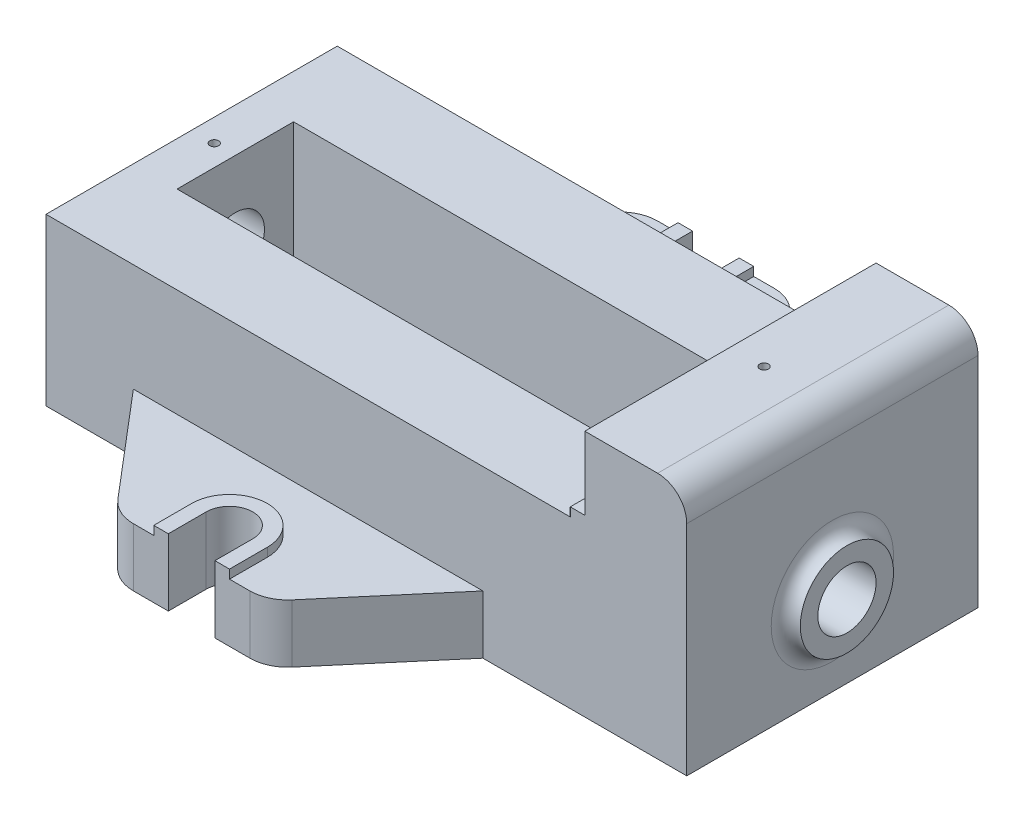
SolidWorks part; units mm, degrees
material "Gray Cast Iron"
ref_plane "Front Plane" through (0, 0, 0) normal (0, 0, 1) x (1, 0, 0)
ref_plane "Top Plane" through (0, 0, 0) normal (0, 1, 0) x (1, 0, 0)
ref_plane "Right Plane" through (0, 0, 0) normal (1, 0, 0) x (0, 0, -1)
sketch "Sketch1" plane through (0, 0, 0) normal (0, 1, 0) x (1, 0, 0)
  line L1 (-90, 50) -> (90, 50)
  line L2 (-90, 50) -> (-90, -50)
  line L3 (-90, -50) -> (90, -50)
  line L4 (90, 50) -> (90, -50)
  line L5 (-90, 50) -> (90, -50) construction
  line L6 (-90, -50) -> (90, 50) construction
  point P0 (0, 0)
  dimension "D1" = 180
  dimension "D2" = 100
extrude "Boss-Extrude1" add sketch "Sketch1" along normal blind 57
sketch "Sketch2" plane through (0, 0, 0) normal (0, 1, 0) x (1, 0, 0)
  line L0 (-90, -50) -> (90, -50) construction
  line L1 (-60, -50) -> (60, -50)
  line L2 (0, -69) -> (0, 49000) construction
  line L3 (-20, -90) -> (-8, -90)
  line L4 (-8, -90) -> (8, -90)
  line L8 (8, -90) -> (20, -90)
  line L9 (-60, -50) -> (-29.9068, -85.4175)
  line L10 (60, -50) -> (29.9068, -85.4175)
  arc A2 (-20, -90) -> (-29.9068, -85.4175) centre (-20, -77) cw
  arc A3 (20, -90) -> (29.9068, -85.4175) centre (20, -77) ccw
  point P18 (-25.4577, -88.7989)
  dimension "D4" = 40
  dimension "D5" = 40
  dimension "D6" = 120
  dimension "D7" = 13
extrude "Boss-Extrude2" add sketch "Sketch2" along normal blind 20
sketch "Sketch3" plane through (0, 20, 0) normal (0, 1, 0) x (1, 0, 0)
  line L0 (0, -1000) -> (0, 49000) construction
  line L1 (-13, -77) -> (-13, -90)
  line L2 (-20, -90) -> (20, -90) construction
  line L3 (13, -77) -> (13, -90)
  line L4 (60, -50) -> (-60, -50) construction
  line L9 (-20, -90) -> (20, -90)
  line L10 (29.9068, -85.4175) -> (60, -50)
  line L11 (60, -50) -> (-60, -50)
  line L12 (-60, -50) -> (-29.9068, -85.4175)
  line L13 (-13, -90) -> (13, -90)
  arc A0 (-13, -77) -> (13, -77) centre (0, -77) cw
  arc A3 (20, -90) -> (29.9068, -85.4175) centre (20, -77) ccw
  arc A4 (-29.9068, -85.4175) -> (-20, -90) centre (-20, -77) ccw
  dimension "D1" = 13
  dimension "D2" = 27
  dimension "D3" = 0
extrude "Boss-Extrude3" add sketch "Sketch3" along normal blind 3
sketch "Sketch4" plane through (0, 23, 0) normal (0, 1, 0) x (1, 0, 0)
  line L0 (8, -77) -> (8, -90)
  line L1 (-13, -90) -> (13, -90) construction
  line L2 (-8, -77) -> (-8, -90)
  arc A0 (-8, -77) -> (8, -77) centre (0, -77) cw
  arc A1 (13, -77) -> (-13, -77) centre (0, -77) ccw construction
  dimension "D1" = 8
extrude "Cut-Extrude2" cut sketch "Sketch4" against normal blind 23 and the other way through all flip side to cut contours L2 A0 L0
mirror "Mirror5" about plane through (0, 0, 0) normal (0, 0, 1) of "Boss-Extrude2"
mirror "Mirror6" about plane through (0, 0, 0) normal (0, 0, 1) of "Boss-Extrude3"
sketch "Sketch5" plane through (0, 23, 0) normal (0, 1, 0) x (1, 0, 0)
  line L0 (-8, 77) -> (-8, 90)
  line L1 (-13, 90) -> (13, 90) construction
  line L2 (8, 77) -> (8, 90)
  arc A0 (8, 77) -> (-8, 77) centre (0, 77) cw
  arc A1 (-13, 77) -> (13, 77) centre (0, 77) ccw construction
  dimension "D1" = 8
extrude "Cut-Extrude3" cut sketch "Sketch5" against normal blind 23 and the other way through all
sketch "Sketch6" plane through (0, 0, 0) normal (0, 0, 1) x (1, 0, 0)
  line L0 (90, 0) -> (130, 0)
  line L1 (130, 0) -> (130, 75)
  line L2 (120, 85) -> (95, 85)
  line L3 (95, 85) -> (95, 60)
  line L4 (95, 60) -> (90, 60)
  line L5 (90, 60) -> (90, 57)
  line L14 (-60, 0) -> (-60, 20)
  line L15 (-60, 20) -> (60, 20)
  line L16 (60, 20) -> (60, 0)
  line L17 (60, 0) -> (90, 0)
  line L18 (90, 0) -> (90, 57)
  line L19 (90, 57) -> (-90, 57)
  line L20 (-90, 57) -> (-90, 0)
  line L21 (-90, 0) -> (-60, 0)
  line L26 (90, 0) -> (90, 57)
  arc A0 (130, 75) -> (120, 85) centre (120, 75) ccw
  point P18 (130, 85)
  dimension "D6" = 10
  dimension "D1" = 40
  dimension "D2" = 85
  dimension "D3" = 35
  dimension "D4" = 25
  dimension "D5" = 0
extrude "Boss-Extrude4" add sketch "Sketch6" along normal mid plane 100 contours L1 A0 L2 L3 L4 L5 L26 L0
sketch "Sketch8" plane through (130, 0, 0) normal (1, 0, 0) x (0, 0, -1)
  circle A0 centre (0, 30) radius 16
  dimension "D1" = 32
  dimension "D2" = 30
  dimension "D3" = 50
extrude "Boss-Extrude5" add sketch "Sketch8" along normal blind 5
sketch "Sketch9" plane through (-90, 0, 0) normal (-1, 0, 0) x (0, 0, 1)
sketch "Sketch11" plane through (-90, 0, 0) normal (-1, 0, 0) x (0, 0, 1)
  circle A0 centre (0, 30) radius 16
  dimension "D1" = 32
  dimension "D2" = 50
  dimension "D3" = 30
extrude "Boss-Extrude6" add sketch "Sketch11" along normal blind 5
sketch "Sketch13" plane through (0, 57, 0) normal (0, 1, 0) x (1, 0, 0)
  line L0 (-1000, 0) -> (49000, 0) construction
  line L2 (-75, 20) -> (90, 20)
  line L3 (-75, 20) -> (-75, -20)
  line L4 (-75, -20) -> (90, -20)
  line L5 (90, 20) -> (90, -20)
  line L6 (90, -50) -> (90, 50) construction
  point P1 (0, 0)
  dimension "D1" = 40
  dimension "D2" = 15
extrude "Cut-Extrude6" cut sketch "Sketch13" against normal through all
sketch "Sketch15" plane through (95, 0, 0) normal (-1, 0, 0) x (0, 0, 1)
  line L0 (0, -1000) -> (0, 49000) construction
  line L1 (50, 60) -> (-50, 60) construction
  circle A0 centre (-30, 72.5) radius 2.5
  circle A1 centre (30, 72.5) radius 2.5
  dimension "D2" = 5
  dimension "D1" = 60
  dimension "D3" = 12.5
hole_wizard "M6 Tapped Hole1" positions "3DSketch1" profile "Sketch16" tap size "M6" standard "ISO"
sketch3d "3DSketch1"
  point P0 (95, 72.5, -30)
  point P3 (95, 72.5, 30)
sketch "Sketch16" plane through (95, 72.5, -30) normal (0, 1, 0) x (0, 0, 1)
  line L0 (0, 0) -> (0, 14.5022)
  line L1 (0, 14.5022) -> (2.5, 13)
  line L2 (2.5, 13) -> (2.5, 0.525)
  line L3 (2.5, 0.525) -> (3.025, 0)
  line L5 (3.025, 0) -> (0, 0)
  line L6 (-2.5, 0.525) -> (-3.025, 0) construction
  line L10 (0, 14.5022) -> (-2.5, 13) construction
  line L11 (0, -6.35) -> (0, 107.95) construction
  dimension "Tap Drill Dia." = 5
  dimension "Tap Drill Depth" = 13
  dimension "Near C'Sink Dia." = 6.05
  dimension "Near C'Sink Angle" = 90
  dimension "Drill Angle" = 118
cosmetic thread "Hole Thread1" parameters "D1"=10, "D2"=6
cosmetic thread "Hole Thread2" parameters "D1"=10, "D2"=6
fillet "Fillet4" radius 5 1 edges at (-90, 30, -16)
sketch "Sketch17" plane through (-95, 0, 0) normal (-1, 0, 0) x (0, 0, 1)
  circle A0 centre (0, 30) radius 10
  dimension "D1" = 20
extrude "Cut-Extrude7" cut sketch "Sketch17" against normal blind 40
fillet "Fillet5" radius 5 1 edges at (130, 30, 16)
sketch "Sketch18" plane through (135, 0, 0) normal (1, 0, 0) x (0, 0, -1)
  circle A0 centre (0, 30) radius 10
  dimension "D1" = 20
extrude "Cut-Extrude8" cut sketch "Sketch18" against normal blind 115
sketch "Sketch19" plane through (0, 57, 0) normal (0, 1, 0) x (1, 0, 0)
  line L0 (-1049.993, 0) -> (48950.007, 0) construction
  circle A0 centre (-82.2304, 0) radius 1.5
  dimension "D1" = 3
extrude "Cut-Extrude9" cut sketch "Sketch19" against normal blind 15
sketch "Sketch20" plane through (0, 85, 0) normal (0, 1, 0) x (1, 0, 0)
  line L0 (-1000, 0) -> (49000, 0) construction
  circle A0 centre (106.5473, 0) radius 1.5
  dimension "D1" = 3
extrude "Cut-Extrude10" cut sketch "Sketch20" against normal blind 46
